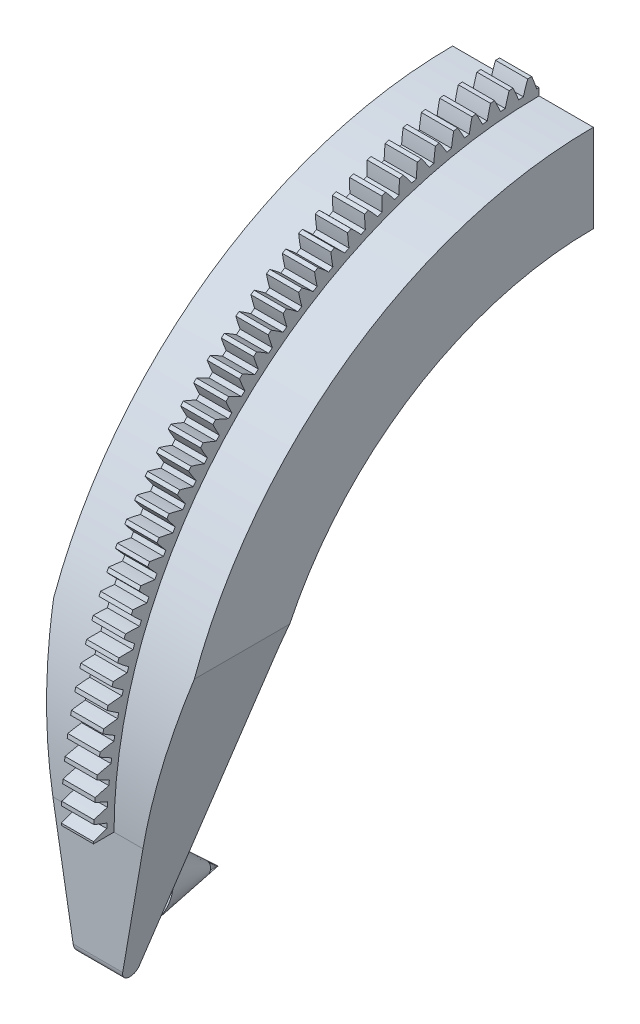
SolidWorks part; units mm, degrees
material "ABS"
ref_plane "Plane1" through (0, 0, 0) normal (0, 0, 1) x (1, 0, 0)
ref_plane "Plane2" through (0, 0, 0) normal (0, 1, 0) x (1, 0, 0)
ref_plane "Plane3" through (0, 0, 0) normal (1, 0, 0) x (0, 0, -1)
other "Configuration Table"
sketch "HoldingSke" plane through (0, 0, 0) normal (0, 1, 0) x (1, 0, 0)
  line L0 (0, 0) -> (-0.866, -0.5)
  line L1 (-15, 0) -> (100, 0) construction
  line L2 (0, 0) -> (-2.1039, 2.3779)
  line L3 (0, 0) -> (-11.863, 4.5341)
  line L4 (0, 0) -> (-7.479, 4.318)
  line L5 (0, 0) -> (-46.8476, -17.4728)
  line L6 (0, 0) -> (-4.5593, -3.0762)
  line L7 (-2.1039, 2.3779) -> (8.6586, 51.2059)
  line L8 (-76.2, 54.61) -> (-75.2, 54.61)
  line L9 (-71.009, 38.7566) -> (-53.1078, 45.2721)
  line L10 (-76.2, 71.12) -> (104.1128, 71.12)
  line L11 (0, 0) -> (-5.5, 0)
  line L12 (-76.2, 101.6) -> (-76.162, 101.6)
  line L13 (24.9733, 27.94) -> (52.9518, 28.4284)
  line L14 (24.9733, 27.94) -> (24.9743, 27.94)
  line L15 (24.9733, 27.94) -> (100.4006, 29.5858)
  line L16 (-63.627, -1) -> (-12.827, -1)
  circle A0 centre (0, 0) radius 4
  circle A1 centre (0, 0) radius 37.5
  circle A2 centre (0, 0) radius 37.5
  circle A3 centre (0, 0) radius 4
  dimension "MHD" = 75
  dimension "Hub_dia" = 75
  dimension "Bore" = 8
  dimension "MBD" = 8
  dimension "Num_teeth" = 150
  dimension "Pitch" = 1
  dimension "Overall_len" = 50
  dimension "Show_teeth" = 150
  dimension "Thickness" = 5.5
  dimension "OAL" = 50.0001
  dimension "T_dim" = 1
  dimension "Ap" = 20
  dimension "H" = 19.05
  dimension "Pitch_radius" = 180.3128
  dimension "Width" = 5.5
  dimension "Backlash" = 0.038
  dimension "Addendum_fac" = 1
  dimension "Dedendum_fac" = 1.25
  dimension "Clearance_fac" = 0.25
  dimension "Dedendum_add" = 0.001
  dimension "Module" = 1
sketch "BasProSke" plane through (0, 0, 0) normal (0, 1, 0) x (1, 0, 0)
  line L0 (-10, 0) -> (60, 0) construction
  line L1 (0, 0) -> (0, 76)
  line L2 (0, 0) -> (5.5, 0)
  line L3 (5.5, 0) -> (5.5, 76)
  line L4 (5.5, 76) -> (0, 76)
  dimension "Thickness" = 5.5
  dimension "Diameter" = 152
revolve "Base-Revolve" add sketch "BasProSke" angle 360 about L0
sketch "TooCutSke" plane through (0, 0, 0) normal (1, 0, 0) x (0, 0, -1)
  line L1 (0, 0) -> (0, 107) construction
  line L2 (0, 0) -> (-0.8519, 74.9952) construction
  line L3 (0, 0) -> (-3.1412, 149.9602) construction
  line L4 (-0.8519, 74.9952) -> (-1.5706, 74.9801) construction
  arc A0 (0.4067, 73.7479) -> (-0.4067, 73.7479) centre (0, 0) ccw
  arc A1 (1.263, 76.0149) -> (-1.263, 76.0149) centre (0, 0) ccw
  circle A2 centre (0, 0) radius 75 construction
  circle A3 centre (0, 0) radius 70.4769 construction
  arc A4 (-0.4067, 73.7479) -> (-1.263, 76.0149) centre (-28.8767, 64.2895) ccw
  arc A5 (1.263, 76.0149) -> (0.4067, 73.7479) centre (28.8767, 64.2895) ccw
  dimension "Root_dia" = 147.498
  dimension "Overcut_dia" = 152.0508
  dimension "Pitch_dia" = 150
  dimension "Base_dia" = 140.9539
  dimension "Flank_rad" = 30
  dimension "Half_ang" = 1.2
  dimension "Half_CT" = 0.7189
extrude "ToothCut" cut sketch "TooCutSke" along normal through all
fillet "Breaks" [suppressed] radius 0.02 tangent propagation no
fillet "RootFillets" [suppressed] radius 0.251
pattern_circular "TeethCuts" count 150 every 2.4 about axis through (-10, 0, 0) along (1, 0, 0) of "ToothCut", "RootFillets", "Breaks"
sketch "HubNeaOneSke" plane through (0, 0, 0) normal (-1, 0, 0) x (0, 0, 1)
  circle A0 centre (0, 0) radius 37.5
  dimension "Diameter" = 75
extrude "HubNearOne" [suppressed] add sketch "HubNeaOneSke" along normal blind 44.5001
sketch "HubNeaBotSke" plane through (0, 0, 0) normal (-1, 0, 0) x (0, 0, 1)
  circle A0 centre (0, 0) radius 37.5
  dimension "Diameter" = 75
extrude "HubNearBoth" [suppressed] add sketch "HubNeaBotSke" along normal blind 22.25
ref_plane "FarPln" through (5.5, 0, 0) normal (1, 0, 0) x (0, 0, -1)
sketch "HubFarSke" plane through (5.5, 0, 0) normal (1, 0, 0) x (0, 0, -1)
  circle A0 centre (0, 0) radius 37.5
  dimension "Diameter" = 75
extrude "HubFar" [suppressed] add sketch "HubFarSke" along normal blind 22.25
sketch "BorSke" plane through (0, 0, 0) normal (1, 0, 0) x (0, 0, -1)
  circle A0 centre (0, 0) radius 4
  dimension "Diameter" = 8
extrude "Bore" cut sketch "BorSke" along normal mid plane 100.0001
sketch "KeySke" plane through (0, 0, 0) normal (1, 0, 0) x (0, 0, -1)
  line L0 (-1, 0) -> (-1, 5)
  line L1 (-1, 5) -> (1, 5)
  line L2 (1, 5) -> (1, 0)
  line L3 (0, 0) -> (0, 34) construction
  line L4 (-1, 0) -> (1, 0)
  dimension "Offset" = 5
  dimension "Width" = 2
extrude "Keyway" [suppressed] cut sketch "KeySke" along normal mid plane 100.0001
pattern_circular "Keyway2" [suppressed] count 2 every 90 about axis through (-10, 0, 0) along (1, 0, 0) reverse direction yes
sketch "ｽｹｯﾁ1" plane through (5.5, 0, 0) normal (1, 0, 0) x (0, 0, -1)
  line L0 (0, 100) -> (0, 72.5)
  line L1 (-72.5, 0) -> (-100, 0)
  arc A0 (-100, 0) -> (0, 100) centre (0, 0) ccw
  arc A1 (0, 72.5) -> (-72.5, 0) centre (0, 0) ccw
  dimension "D1" = 200
  dimension "D2" = 145
extrude "ｶｯﾄ - 押し出し1" cut sketch "ｽｹｯﾁ1" against normal through all
ref_plane "平面1" through (5.5, 0, 72.5) normal (0, -1, 0) x (-1, 0, 0)
ref_plane "平面2" through (2.75, 0, 0) normal (1, 0, 0) x (0, 0, -1)
sketch "ｽｹｯﾁ2" plane through (2.75, 0, 0) normal (1, 0, 0) x (0, 0, -1)
  line L0 (0, 72.5) -> (0, 57.5)
  line L2 (-72.5, 0) -> (-72.5, -20)
  line L3 (-69.6011, -20.5413) -> (-53.6262, 20.748)
  arc A0 (0, 72.5) -> (-72.5, 0) centre (0, 0) ccw construction
  arc A1 (0, 72.5) -> (-72.5, 0) centre (0, 0) ccw
  arc A2 (0, 57.5) -> (-53.6262, 20.748) centre (0, 0) ccw
  arc A3 (-72.5, -20) -> (-69.6011, -20.5413) centre (-71, -20) ccw
  point P3 (-72.5, -31.3609)
  dimension "D1" = 115
  dimension "D2" = 1.5
  dimension "D3" = 20
extrude "ﾎﾞｽ - 押し出し1" add sketch "ｽｹｯﾁ2" along normal blind 12 and the other way blind 12
sketch "ｽｹｯﾁ3" plane through (0, 0, 72.5) normal (0, 0, 1) x (1, 0, 0)
  line L0 (-9.25, 25) -> (0.25, -30)
  line L1 (0.25, -30) -> (5.25, -30)
  line L2 (5.25, -30) -> (14.75, 25)
  line L4 (14.75, 0) -> (14.75, 72.5) construction
  line L5 (-9.25, 72.5) -> (-9.25, 0) construction
  line L6 (14.75, 0) -> (14.75, 25)
  line L7 (-9.25, 25) -> (-9.25, 0)
  line L8 (5.5, 0) -> (14.75, 0) construction
  line L9 (-9.25, 0) -> (-9.25, -20) construction
  line L10 (-9.25, 0) -> (-9.25, -30)
  line L11 (-9.25, -30) -> (0.25, -30)
  line L12 (5.25, -30) -> (14.75, -30)
  line L13 (14.75, -30) -> (14.75, 0)
  line M2 (-9.25, -20) -> (14.75, -20)
  line M3 (14.75, -20) -> (14.75, 0)
  line M4 (14.75, 0) -> (5.5, 0)
  line M6 (0, 0) -> (-9.25, 0)
  line M7 (-9.25, 0) -> (-9.25, -20)
  dimension "D1" = 25
  dimension "D2" = 30
  dimension "D3" = 5
  dimension "D4" = 9.5
extrude "ｶｯﾄ - 押し出し2" cut sketch "ｽｹｯﾁ3" against normal through all contours L10 L11 L0 M2 | L12 L13 L2 M2 | L2 M2 M3 M4 | L0 M6 M7 M2 | L0 L7 M6 | L6 L2 M4 region at (-7.8106, 8.3333, 72.5) region at (-6.145, -10.9524, 72.5) region at (-4.9174, -25.1667, 72.5) region at (10.4174, -25.1667, 72.5) region at (11.645, -10.9524, 72.5) region at (13.3106, 8.3333, 72.5)
ref_plane "平面3" through (2.75, 0, 0) normal (-1, 0, 0) x (0, 0, 1)
sketch "ｽｹｯﾁ4" plane through (2.75, 0, 0) normal (1, 0, 0) x (0, 0, -1)
  line L0 (-69.6011, -20.5413) -> (-53.6262, 20.748)
  line L1 (-65.9927, -11.215) -> (-63.8277, -5.6192)
  line L2 (-65.9927, -11.215) -> (-52.0033, -16.6275)
  line L3 (-52.0033, -16.6275) -> (-63.8277, -5.6192)
  line L4 (-49.7965, 28.75) -> (-36.8061, 21.25)
  line L5 (-36.8061, 21.25) -> (-45.3242, 35.3832)
  line L6 (0, 57.5) -> (0, 72.5) construction
  arc A0 (0, 57.5) -> (-53.6262, 20.748) centre (0, 0) ccw
  arc A1 (-45.3242, 35.3832) -> (-53.6262, 20.748) centre (0, 0) ccw
  point P9 (-63.1696, -3.9183)
  point P11 (-49.6559, 28.992)
  point P12 (0, 0)
  dimension "D1" = 15
  dimension "D2" = 15
  dimension "D3" = 6
  dimension "D4" = 10
  dimension "D5" = 8
  dimension "D6" = 60
revolve "回転1" add sketch "ｽｹｯﾁ4" angle 360 about L2
revolve "回転2" add sketch "ｽｹｯﾁ4<5>" angle 360 about L4 region at (2.75, 28.5056, 44.0201)
sketch "ｽｹｯﾁ4<5>" plane through (2.75, 0, 0) normal (1, 0, 0) x (0, 0, -1) same geometry as "ｽｹｯﾁ4"
equation "' \"Module@HoldingSke\" = 6.35"
equation "' \"Num_teeth@HoldingSke\" = 12"
equation "' \"Ap@HoldingSke\" =  20"
equation "' \"Ap@HoldingSke\" = 20"
equation "' \"Width@HoldingSke\" = 0.5 * 25.4"
equation "' \"Hub_dia@HoldingSke\"= 1 * 25.4"
equation "' \"Hub_dia@HoldingSke\" = 1 * 25.4"
equation "' \"Overall_len@HoldingSke\" = 1.0 * 25.4"
equation "' \"Bore@HoldingSke\" = 0.75 * 25.4"
equation "' \"T_dim@HoldingSke\" = 0.1 * 25.4"
equation "' \"Width@KeySke\" = 0.25 * 25.4"
equation "' \"Show_teeth@HoldingSke\" = 13"
equation "' \"Backlash@HoldingSke\" = 0.009 * 25.4"
equation "' \"Addendum_fac@HoldingSke\" = 1.0"
equation "' \"Dedendum_fac@HoldingSke\" = 1.25"
equation "' \"Dedendum_add@HoldingSke\" = 0.00005 * 25.4"
equation "' \"Clearance_fac@HoldingSke\" = 0.25"
equation "\"Pitch@HoldingSke\" = 1 / \"Module@HoldingSke\""
equation "\"Overcut_dia@TooCutSke\" = (\"Num_teeth@HoldingSke\" + 2 * \"Addendum_fac@HoldingSke\") / \"Pitch@HoldingSke\" + 0.002 * 25.4"
equation "\"Pitch_dia@TooCutSke\" = \"Num_teeth@HoldingSke\" / \"Pitch@HoldingSke\""
equation "\"Base_dia@TooCutSke\" = \"Num_teeth@HoldingSke\" / \"Pitch@HoldingSke\" * cos((\"Ap@HoldingSke\"  * 3.14159265 / 180))"
equation "\"Root_dia@TooCutSke\" = (\"Num_teeth@HoldingSke\" + 2) / \"Pitch@HoldingSke\" - 2 * (\"Addendum_fac@HoldingSke\" + \"Dedendum_fac@HoldingSke\") / \"Pitch@HoldingSke\" - \"Dedendum_add@HoldingSke\" * 2"
equation "\"Half_ang@TooCutSke\" = 180 / \"Num_teeth@HoldingSke\""
equation "\"Half_CT@TooCutSke\" = \"Num_teeth@HoldingSke\" / \"Pitch@HoldingSke\" * sin((3.14159265 / 2 / \"Num_teeth@HoldingSke\")) / 2 - 7 * \"Backlash@HoldingSke\" / 4"
equation "\"Flank_rad@TooCutSke\" = \"Num_teeth@HoldingSke\" / \"Pitch@HoldingSke\" / 5"
equation "\"Radius@RootFillets\" = \"Clearance_fac@HoldingSke\" / \"Pitch@HoldingSke\" + \"Dedendum_add@HoldingSke\""
equation "\"Break_rad@Breaks\" = 0.02 / \"Pitch@HoldingSke\""
equation "\"Thickness@HoldingSke\" = \"Width@HoldingSke\""
equation "\"OAL@HoldingSke\" = \"Thickness@HoldingSke\""
equation "\"MHD@HoldingSke\" = (\"Num_teeth@HoldingSke\" + 2) / \"Pitch@HoldingSke\" - 2 * (\"Addendum_fac@HoldingSke\" + \"Dedendum_fac@HoldingSke\")  / \"Pitch@HoldingSke\" - \"Dedendum_add@HoldingSke\" * 2"
equation "\"MBD@HoldingSke\" = (\"Num_teeth@HoldingSke\" + 2) / \"Pitch@HoldingSke\" - 2 * (\"Addendum_fac@HoldingSke\" + \"Dedendum_fac@HoldingSke\")  / \"Pitch@HoldingSke\" - \"Dedendum_add@HoldingSke\" * 2 - 0.002 * 25.4"
equation "\"MHD@HoldingSke\" = ((sgn( \"MHD@HoldingSke\" - \"Hub_dia@HoldingSke\" )-1)*( \"MHD@HoldingSke\" - \"Hub_dia@HoldingSke\" ))/-2+ \"Hub_dia@HoldingSke\""
equation "\"MBD@HoldingSke\" = ((sgn( \"MBD@HoldingSke\" - \"Bore@HoldingSke\" )-1)*( \"MBD@HoldingSke\" - \"Bore@HoldingSke\" ))/-2+ \"Bore@HoldingSke\""
equation "\"OAL@HoldingSke\" = ((sgn( \"OAL@HoldingSke\" - \"Overall_len@HoldingSke\" )+1)*( \"OAL@HoldingSke\" - \"Overall_len@HoldingSke\" ))/2 + \"Overall_len@HoldingSke\" + 0.000002 * 25.4"
equation "\"Num_teeth@TeethCuts\" = int( \"Show_teeth@HoldingSke\" ) + 1"
equation "\"Num_teeth@TeethCuts\" = ((sgn( \"Num_teeth@TeethCuts\" - \"Num_teeth@HoldingSke\" )-1)*( \"Num_teeth@TeethCuts\" - \"Num_teeth@HoldingSke\" ))/-2+ \"Num_teeth@HoldingSke\""
equation "\"Num_teeth@TeethCuts\" = ((sgn( \"Num_teeth@TeethCuts\" - 2.0)+1)*( \"Num_teeth@TeethCuts\" - 2.0))/2 +2.0"
equation "\"Angle@TeethCuts\" = 360.0 / \"Num_teeth@HoldingSke\""
equation "\"Diameter@BasProSke\" = (\"Num_teeth@HoldingSke\" + 2 * \"Addendum_fac@HoldingSke\") / \"Pitch@HoldingSke\""
equation "\"Thickness@BasProSke\"  = \"Thickness@HoldingSke\""
equation "' \"Fillet_rad@BasProSke\" =  \"Thickness@HoldingSke\" * 0.05"
equation "' \"Fillet_rad@BasProSke\" = \"Thickness@HoldingSke\" * 0.05"
equation "\"MHD@HoldingSke\" = ((sgn( \"MHD@HoldingSke\" - \"Root_dia@TooCutSke\" )-1)*( \"MHD@HoldingSke\" - \"Root_dia@TooCutSke\" ))/-2+ \"Root_dia@TooCutSke\""
equation "\"Diameter@HubNeaOneSke\" = \"MHD@HoldingSke\""
equation "\"Length@HubNearOne\" = \"OAL@HoldingSke\" - \"Thickness@BasProSke\""
equation "\"Diameter@HubNeaBotSke\" = \"MHD@HoldingSke\""
equation "\"Length@HubNearBoth\" = ( \"OAL@HoldingSke\" - \"Thickness@BasProSke\" ) / 2.0"
equation "\"Thickness@FarPln\" = \"Thickness@BasProSke\""
equation "\"Diameter@HubFarSke\" = \"MHD@HoldingSke\""
equation "\"Length@HubFar\" = ( \"OAL@HoldingSke\" - \"Thickness@BasProSke\" ) / 2.0"
equation "\"Diameter@BorSke\" = \"MBD@HoldingSke\""
equation "\"D1@Bore\" = \"OAL@HoldingSke\" * 2.0"
equation "\"D1@Keyway\" = \"OAL@HoldingSke\" * 2.0"
equation "\"Offset@KeySke\" = \"T_dim@HoldingSke\" + \"MBD@HoldingSke\" / 2.0"
